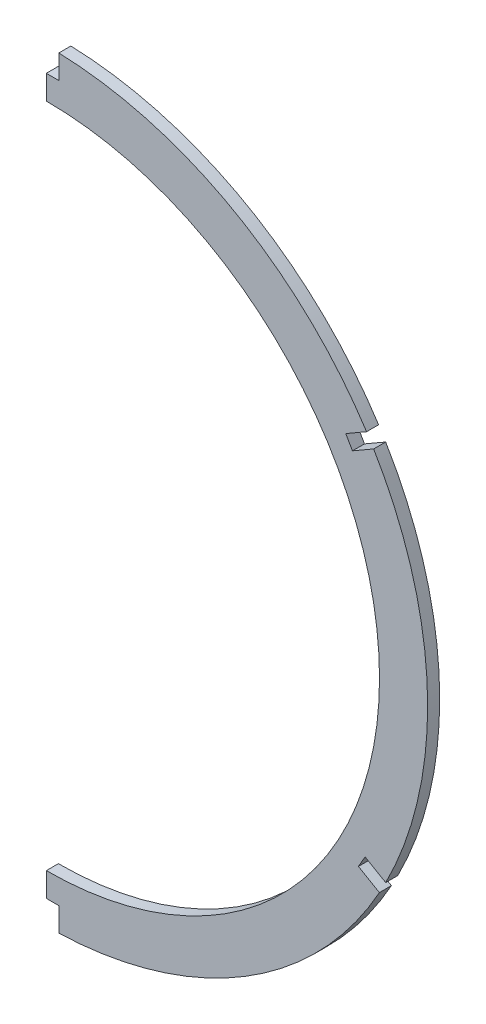
SolidWorks part; units mm, degrees
material "Balsa"
ref_plane "Front Plane" through (0, 0, 0) normal (0, 0, 1) x (1, 0, 0)
ref_plane "Top Plane" through (0, 0, 0) normal (0, 1, 0) x (1, 0, 0)
ref_plane "Right Plane" through (0, 0, 0) normal (1, 0, 0) x (0, 0, -1)
sketch "Sketch2" plane through (0, 0, 0) normal (0, 0, 1) x (1, 0, 0)
  line L0 (0, 0) -> (0, 240.9936) construction
  line L1 (-1.7839, 106.6642) -> (-1.7839, 99.822) construction
  line L2 (1.7839, 106.6642) -> (1.7839, 99.822) construction
  line L3 (-1.7839, 99.822) -> (1.7839, 99.822) construction
  line L4 (-87.7705, -42.8471) -> (-87.8712, -42.9053) construction
  line L5 (-604.1774, -338.907) -> (0, 9.8743) construction
  line L6 (-89.5483, -39.7674) -> (-83.8289, -36.4657) construction
  line L7 (-87.7705, -42.8471) -> (-82.0511, -39.5454) construction
  line L8 (-83.8289, -36.4657) -> (-82.0511, -39.5454) construction
  line L9 (604.1774, -338.907) -> (0, 9.8743) construction
  line L10 (87.7705, -42.8471) -> (82.0511, -39.5454) construction
  line L11 (87.7705, -42.8471) -> (87.8712, -42.9053) construction
  line L12 (89.5483, -39.7674) -> (83.8289, -36.4657) construction
  line L13 (83.8289, -36.4657) -> (82.0511, -39.5454) construction
  arc A0 (-7.652, 93.6463) -> (7.652, 93.6463) centre (0, 6.0782) ccw
  arc A1 (-1.7839, 106.6642) -> (-89.5483, -39.7674) centre (0, 6.0782) ccw
  arc A6 (-1.778, 93.962) -> (-7.652, 93.6463) centre (0, 6.0782) ccw
  circle A7 centre (0, 6.0782) radius 87.9018 construction
  arc A8 (0, 93.98) -> (-1.778, 93.962) centre (0, 6.0782) ccw
  arc A9 (1.778, 93.962) -> (0, 93.98) centre (0, 6.0782) ccw
  arc A10 (1.778, 93.962) -> (0, 93.98) centre (0, 6.0782) ccw construction
  arc A12 (7.652, 93.6463) -> (1.778, 93.962) centre (0, 6.0782) ccw
  arc A13 (0, 93.98) -> (-1.778, 93.962) centre (0, 6.0782) ccw construction
  arc A15 (7.652, 93.6463) -> (1.778, 93.962) centre (0, 6.0782) ccw construction
  arc A16 (-1.778, 93.962) -> (-7.652, 93.6463) centre (0, 6.0782) ccw construction
  arc A17 (0, 106.68) -> (-1.7839, 106.6642) centre (0, 6.0782) ccw
  circle A18 centre (0, 6.0782) radius 100.6018 construction
  arc A19 (1.7839, 106.6642) -> (0, 106.68) centre (0, 6.0782) ccw
  arc A20 (-87.8712, -42.9053) -> (87.8712, -42.9053) centre (0, 6.0782) ccw
  arc A21 (-89.5483, -39.7674) -> (-88.7234, -41.3442) centre (0, 6.0782) ccw
  arc A22 (-88.7234, -41.3442) -> (-87.8712, -42.9053) centre (0, 6.0782) ccw
  arc A23 (87.8712, -42.9053) -> (88.7234, -41.3442) centre (0, 6.0782) ccw
  arc A24 (89.5483, -39.7674) -> (1.7839, 106.6642) centre (0, 6.0782) ccw
  arc A25 (88.7234, -41.3442) -> (89.5483, -39.7674) centre (0, 6.0782) ccw
  point P25 (0, 99.822)
  dimension "D3" = 119.997
  dimension "D8" = 12.7
  dimension "D6" = 87.9018
  dimension "D2" = 1.7839
  dimension "D4" = 9.8743
  dimension "D5" = 3.556
  dimension "D1" = 93.98
  dimension "D7" = 5.842
  dimension "D9" = 6.604
  dimension "D10" = 3.556
extrude "Boss-Extrude1" add sketch "Sketch2" against normal blind 3.175
sketch "Sketch3" plane through (0, 0, 0) normal (1, 0, 0) x (0, 0, -1)
  line L5 (-72.4915, 152.7087) -> (76.812, 152.7087)
  line L6 (-72.4915, 152.7087) -> (-72.4915, -135.9702)
  line L7 (-72.4915, -135.9702) -> (76.812, -135.9702)
  line L8 (76.812, 152.7087) -> (76.812, -135.9702)
extrude "Cut-Extrude1" cut sketch "Sketch3" against normal through all
sketch "Sketch4" plane through (0, 0, 0) normal (0, 0, 1) x (1, 0, 0)
  line L0 (-88.1091, 62.7761) -> (-78.9966, 57.515)
  line L3 (-89.8744, 59.7185) -> (-88.1091, 62.7761)
  line L4 (0, 9.8679) -> (0, -96.8576) construction
  line L5 (0, 0) -> (0, 151.9186) construction
  line L6 (-88.9918, 61.2473) -> (-79.8792, 55.9862) construction
  line L7 (-89.8744, 59.7185) -> (-80.7619, 54.4574)
  line L8 (-80.7619, 54.4574) -> (-78.9966, 57.515)
  line L9 (-79.8792, 55.9862) -> (0, 9.8679) construction
  line L10 (0, 9.8679) -> (-60.4839, 9.8679) construction
  line L11 (-88.9918, -41.5115) -> (-79.8792, -36.2504) construction
  line L12 (-84.095, -36.646) -> (-82.3297, -39.7036)
  line L13 (-92.2228, -41.3386) -> (-84.095, -36.646)
  line L14 (-92.2228, -41.3386) -> (-90.4575, -44.3962)
  line L15 (-90.4575, -44.3962) -> (-82.3297, -39.7036)
  line L16 (-79.8792, -36.2504) -> (0, 9.8679) construction
  line L17 (3.302, -88.1737) -> (-3.302, -88.1737)
  line L18 (-3.302, -88.1737) -> (-3.302, -95.6228)
  line L19 (79.8792, -36.2504) -> (0, 9.8679) construction
  line L20 (-3.302, -95.6228) -> (3.302, -95.6228)
  line L21 (0, -95.6228) -> (0, -88.1737)
  line L22 (-3.302, 110.2958) -> (3.302, 110.2958)
  line L23 (-3.302, 110.2958) -> (-3.302, 100.33)
  line L24 (-3.302, 100.33) -> (3.302, 100.33)
  line L25 (0, 110.2958) -> (0, 100.33)
  line L26 (88.9918, -41.5115) -> (79.8792, -36.2504) construction
  line L27 (0, 9.8679) -> (60.4839, 9.8679) construction
  line L28 (79.8792, 55.9862) -> (0, 9.8679) construction
  line L29 (88.9918, 61.2473) -> (79.8792, 55.9862) construction
  line L30 (3.302, 110.2958) -> (3.302, 100.33)
  line L31 (3.302, -88.1737) -> (3.302, -95.6228)
  line L32 (90.4575, -44.3962) -> (82.3297, -39.7036)
  line L33 (92.2228, -41.3386) -> (90.4575, -44.3962)
  line L34 (92.2228, -41.3386) -> (84.095, -36.646)
  line L35 (84.095, -36.646) -> (82.3297, -39.7036)
  line L36 (80.7619, 54.4574) -> (78.9966, 57.515)
  line L37 (89.8744, 59.7185) -> (80.7619, 54.4574)
  line L38 (89.8744, 59.7185) -> (88.1091, 62.7761)
  line L39 (88.1091, 62.7761) -> (78.9966, 57.515)
  point P2 (-74.38, 52.8112)
  point P12 (-83.2124, -38.1748)
  point P19 (-77.7131, -34.9998)
  point P24 (0, -81.8237)
  point P27 (0, 93.98)
  point P49 (77.7131, -34.9998)
  point P50 (83.2124, -38.1748)
  point P51 (74.38, 52.8112)
  arc M17 (0, -94.5237) -> (0, 106.68) centre (0, 6.0782) ccw
  line M18 (0, 106.68) -> (0, 93.98)
  line M20 (0, -81.8237) -> (0, -94.5237)
  dimension "D1" = 60
  dimension "D2" = 9.8679
  dimension "D3" = 3.5306
  dimension "D4" = 85.8866
  dimension "D5" = 6.35
  dimension "D6" = 89.7354
  dimension "D7" = 6.35
  dimension "D8" = 3.5306
  dimension "D9" = 3.302
  dimension "D10" = 91.6916
  dimension "D11" = 6.35
  dimension "D12" = 84.1121
  dimension "D13" = 6.35
  dimension "D14" = 3.302
extrude "Cut-Extrude2" cut sketch "Sketch4" against normal through all contours L30 L22 L25 M17 | L30 L24 M17 M18 | L34 L35 L32 M17 | L31 L17 M20 M17 | L39 L36 L37 M17 region at (1.6486, -91.3396, 0) region at (1.6486, 103.496, 0) region at (1.6551, 108.4789, 0) region at (82.6583, 57.5846, 0) region at (85.9605, -39.7676, 0)
